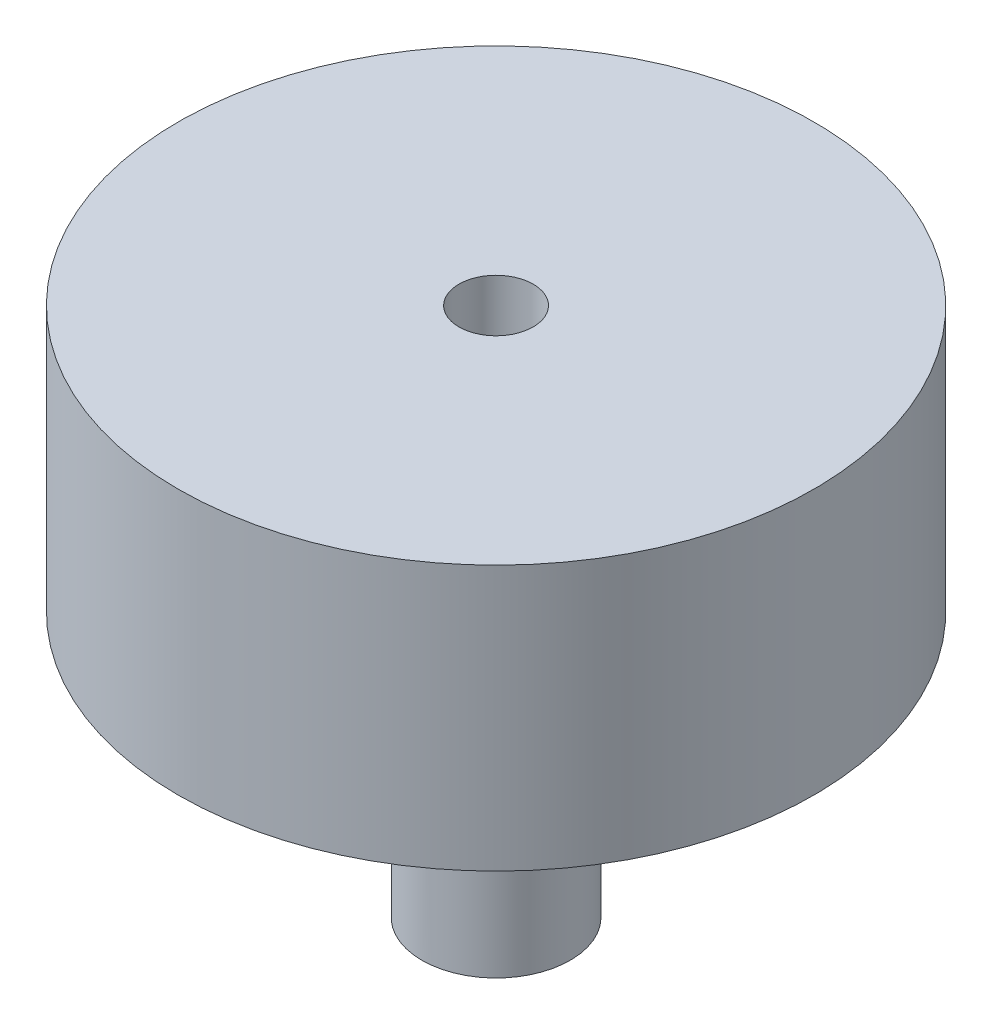
SolidWorks part; units mm, degrees
ref_plane "Front Plane" through (0, 0, 0) normal (0, 0, 1) x (1, 0, 0)
ref_plane "Top Plane" through (0, 0, 0) normal (0, 1, 0) x (1, 0, 0)
ref_plane "Right Plane" through (0, 0, 0) normal (1, 0, 0) x (0, 0, -1)
sketch "Sketch5" plane through (0, 0, 0) normal (0, 1, 0) x (1, 0, 0)
  circle A0 centre (0, 0) radius 30
  circle A1 centre (0, 0) radius 3.5
  circle A2 centre (0, 0) radius 7
extrude "Boss-Extrude5" add sketch "Sketch5" along normal blind 25 contours A0 A2 region at (-29.1515, 0, 0)
extrude "Boss-Extrude6" add sketch "Sketch5<6>" along normal blind 25 contours A2
sketch "Sketch5<6>" plane through (0, 0, 0) normal (0, 1, 0) x (1, 0, 0) same geometry as "Sketch5"
extrude "Cut-Extrude1" cut sketch "Sketch5<8>" along normal blind 25 contours A1 region at (0, 0, 0)
sketch "Sketch5<8>" plane through (0, 0, 0) normal (0, 1, 0) x (1, 0, 0) same geometry as "Sketch5"
extrude "Boss-Extrude7" add sketch "Sketch5<9>" against normal blind 25 contours A2 A1 region at (-6.802, 0, 0)
sketch "Sketch5<9>" plane through (0, 0, 0) normal (0, 1, 0) x (1, 0, 0) same geometry as "Sketch5"
ref_plane "Plane1" through (0, 0, 10) normal (0, 0, 1) x (1, 0, 0)
hole_wizard "CBORE for M5 Hex Head Bolt1" positions "Sketch8" profile "Sketch9" counterbore size "M5" standard "ANSI Metric" end condition through all
sketch "Sketch8" plane through (0, 0, 10) normal (0, 0, 1) x (1, 0, 0)
  point P0 (0, -10.7188)
sketch "Sketch9" plane through (0, -10.7188, 10) normal (1, 0, 0) x (0, -1, 0)
  line L0 (0, 0) -> (0, 40)
  line L1 (0, 40) -> (2.75, 40)
  line L3 (2.75, 40) -> (2.75, 3.58)
  line L4 (6.12, 3.58) -> (2.75, 3.58)
  line L5 (6.12, 3.58) -> (6.12, 0.025)
  line L6 (6.12, 0.025) -> (6.145, 0)
  line L7 (6.145, 0) -> (0, 0)
  line L8 (-6.12, 0.025) -> (-6.145, 0) construction
  line L11 (0, -6.35) -> (0, 107.95) construction
  dimension "Thru Hole Dia." = 5.5
  dimension "Thru Hole Depth" = 40
  dimension "C'Bore Dia." = 12.24
  dimension "C'Bore Depth" = 3.58
  dimension "Near C'Sink Dia." = 12.29
  dimension "Near C'Sink Angle" = 90
